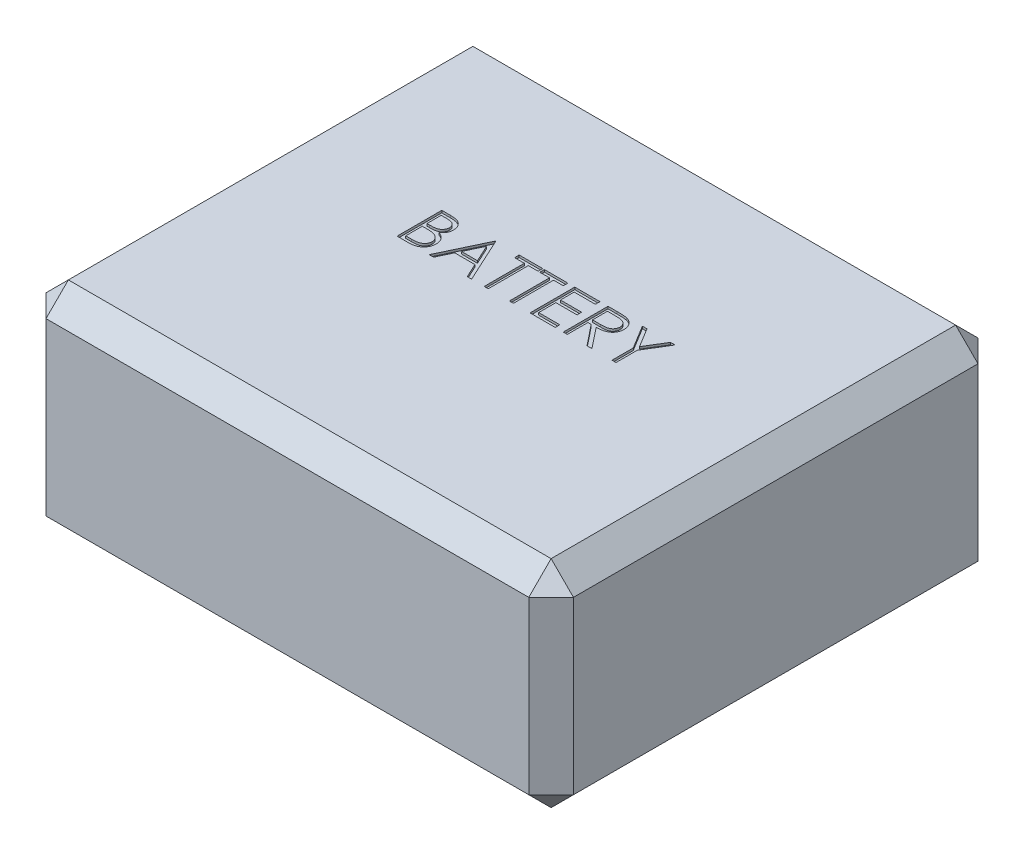
SolidWorks part; units mm, degrees
ref_plane "Front Plane" through (0, 0, 0) normal (0, 0, 1) x (1, 0, 0)
ref_plane "Top Plane" through (0, 0, 0) normal (0, 1, 0) x (1, 0, 0)
ref_plane "Right Plane" through (0, 0, 0) normal (1, 0, 0) x (0, 0, -1)
sketch "Sketch1" plane through (0, 0, 0) normal (0, 1, 0) x (1, 0, 0)
  line L1 (0, 0) -> (236, 0)
  line L2 (0, 0) -> (0, 201)
  line L3 (0, 201) -> (236, 201)
  line L4 (236, 0) -> (236, 201)
  dimension "D1" = 201
  dimension "D2" = 236
extrude "Boss-Extrude1" add sketch "Sketch1" along normal blind 96.5
sketch "Sketch2" plane through (0, 96.5, 0) normal (0, 1, 0) x (1, 0, 0)
  line L0 (0, 100.5) -> (236, 100.5) construction
  line L1 (0, 201) -> (0, 0) construction
  line L2 (236, 0) -> (236, 201) construction
  text T0 "BATTERY" font "Century Gothic" height 20
extrude "Cut-Extrude1" cut sketch "Sketch2" against normal blind 1
chamfer "Chamfer1" distance 10 angle 45 12 edges at (0, 96.5, -100.5) (0, 0, -100.5) (118, 96.5, -201) (0, 48.25, -201) (118, 0, -201) (236, 96.5, -100.5) (236, 48.25, -201) (236, 0, -100.5) (0, 48.25, 0) (118, 96.5, 0) (236, 48.25, 0) (118, 0, 0)
